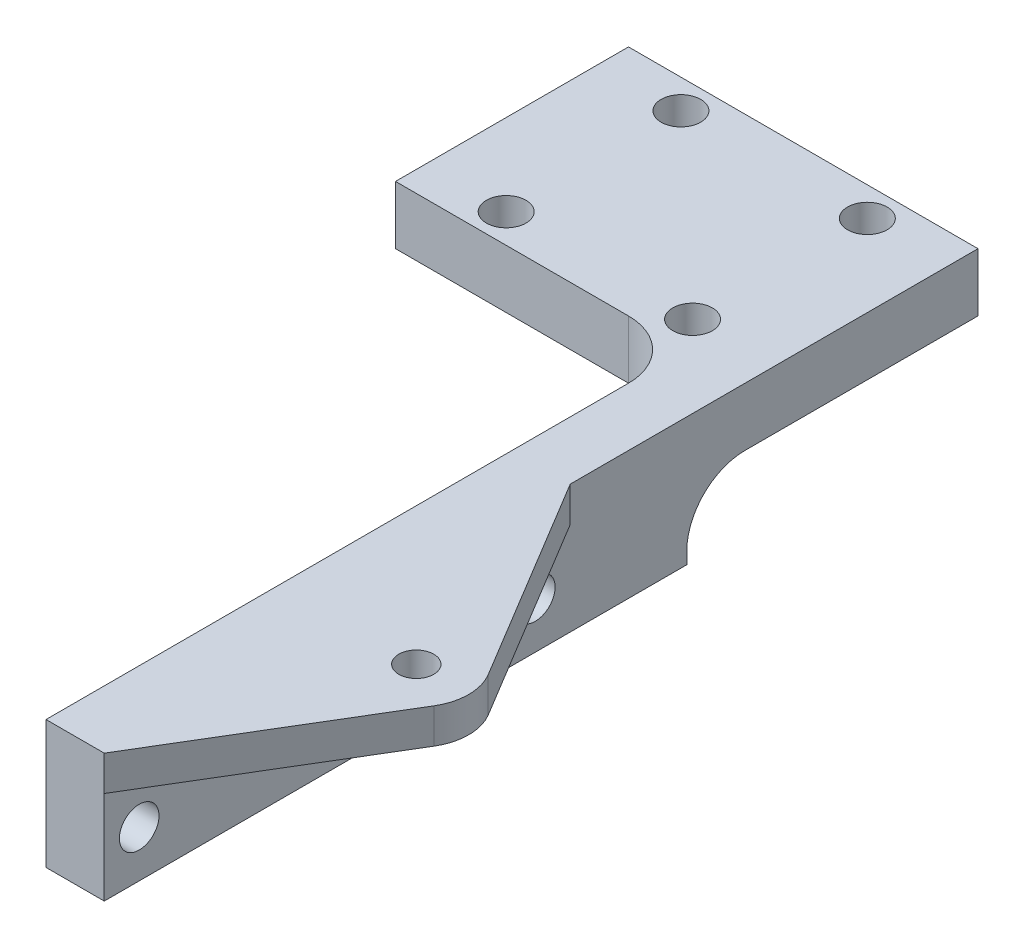
SolidWorks part; units mm, degrees
ref_plane "Front Plane" through (0, 0, 0) normal (0, 0, 1) x (1, 0, 0)
ref_plane "Top Plane" through (0, 0, 0) normal (0, 1, 0) x (1, 0, 0)
ref_plane "Right Plane" through (0, 0, 0) normal (1, 0, 0) x (0, 0, -1)
sketch "Sketch2" plane through (0, 0, 0) normal (1, 0, 0) x (0, 0, -1)
  line L0 (3.0688, 10.3579) -> (3.0688, 21.3579)
  line L1 (3.0688, 21.3579) -> (-36.9312, 21.3579)
  line L2 (-36.9312, 21.3579) -> (-36.9312, 10.3579)
  line L3 (-36.9312, 10.3579) -> (3.0688, 10.3579)
  line L5 (3.0688, 21.3579) -> (18.0688, 21.3579)
  line L6 (3.0688, 21.3579) -> (3.0688, 10.3579)
  line L7 (3.0688, 10.3579) -> (18.0688, 10.3579)
  line L8 (18.0688, 21.3579) -> (18.0688, 10.3579)
  circle A0 centre (0.0688, 14.3579) radius 1.7
  circle A1 centre (-33.9312, 14.3579) radius 1.7
extrude "Boss-Extrude1" add sketch "Sketch2" along normal blind 5 contours L8 L5 L0 L7 | L2 L3 L0 L1 A1 A0 region at (0, 15.9225, 16.9312) region at (0, 15.8579, -10.5688)
sketch "Sketch3" plane through (0, 21.3579, 0) normal (0, 1, 0) x (1, 0, 0)
  line L0 (-25, 38.0688) -> (-25, 18.0688)
  line L1 (-25, 18.0688) -> (5, 18.0688)
  line L2 (5, 18.0688) -> (5, 38.0688)
  line L3 (5, 38.0688) -> (-25, 38.0688)
  line L4 (0, -36.9312) -> (0, 18.0688) construction
  line L5 (0, -36.9312) -> (0, 18.0688)
  line L6 (5, -36.9312) -> (5, 18.0688) construction
  line L7 (5, -36.9312) -> (5, 18.0688)
  circle A0 centre (-2, 20.5688) radius 1.7
  circle A1 centre (-2, 35.5688) radius 1.7
  circle A2 centre (-18, 20.5688) radius 1.7
  circle A3 centre (-18, 35.5688) radius 1.7
  line M4 (5, 18.0688) -> (0, 18.0688)
extrude "Boss-Extrude2" add sketch "Sketch3" against normal blind 5 contours L2 L3 L0 L1 A3 A2 A1 A0 M4 region at (-10, 21.3579, -28.0688)
sketch "Sketch4" plane through (0, 0, -18.0688) normal (0, 0, -1) x (-1, 0, 0)
  line L4 (0, 10.3579) -> (0, 16.3579)
  line L5 (0, 16.3579) -> (-5, 16.3579)
  line L6 (-5, 16.3579) -> (-5, 10.3579)
  line L7 (-5, 10.3579) -> (0, 10.3579)
  line L8 (0, 10.3579) -> (0, 16.3579)
  line L9 (0, 16.3579) -> (-5, 16.3579)
  line L10 (-5, 16.3579) -> (-5, 10.3579)
  line L11 (-5, 10.3579) -> (0, 10.3579)
  dimension "D1" = 0
extrude "Cut-Extrude1" cut sketch "Sketch4" against normal blind 5
fillet "Fillet1" radius 5 1 edges at (2.5, 16.3579, -13.0688)
fillet "Fillet2" radius 5 1 edges at (0, 18.8579, -18.0688)
sketch "Sketch5" plane through (0, 21.3579, 0) normal (0, 1, 0) x (1, 0, 0)
  line L0 (5, -1.6312) -> (5, 1.7688) construction
  line L1 (5, -35.6312) -> (5, -32.2312) construction
  line L2 (5, -1.6312) -> (5, 1.7688)
  line L3 (5, -35.6312) -> (5, -32.2312)
  line L4 (5, -32.2312) -> (5, -1.6312)
  line L5 (5, -16.9312) -> (11.7846, -16.9312)
  line L6 (15.6402, -19.2516) -> (5, -36.9312)
  line L7 (15.6402, -14.6107) -> (5, 3.0688)
  line L14 (0, 13.0688) -> (0, -36.9312)
  line L15 (0, -36.9312) -> (5, -36.9312)
  line L16 (5, -36.9312) -> (5, 38.0688)
  line L17 (5, 38.0688) -> (-25, 38.0688)
  line L18 (-25, 38.0688) -> (-25, 18.0688)
  line L19 (-25, 18.0688) -> (-5, 18.0688)
  line L20 (0, 13.0688) -> (0, -36.9312)
  line L21 (0, -36.9312) -> (5, -36.9312)
  line L22 (5, -36.9312) -> (5, 38.0688)
  line L23 (5, 38.0688) -> (-25, 38.0688)
  line L24 (-25, 38.0688) -> (-25, 18.0688)
  line L25 (-25, 18.0688) -> (-5, 18.0688)
  circle A0 centre (11.7846, -16.9312) radius 1.5
  circle A1 centre (11.7846, -16.9312) radius 4.5
  arc A3 (0, 13.0688) -> (-5, 18.0688) centre (-5, 13.0688) ccw
  arc A4 (0, 13.0688) -> (-5, 18.0688) centre (-5, 13.0688) ccw
  line M12 (5, -36.9312) -> (5, 38.0688)
  dimension "D1" = 3
  dimension "D2" = 0
extrude "Boss-Extrude3" add sketch "Sketch5" against normal blind 3 contours A1 L5 L6 M12 | A1 L7 L4 L5 M12 | A1 A0 region at (7.9582, 21.3579, 8.5022) region at (7.9582, 21.3579, 25.3602) region at (10.6146, 21.3579, 12.7179)
sketch "Sketch6" plane through (0, 0, 36.9312) normal (0, 0, 1) x (1, 0, 0)
  line L5 (0, 21.3579) -> (0, 10.3579)
  line L6 (0, 10.3579) -> (5, 10.3579)
  line L7 (5, 10.3579) -> (5, 18.3579)
  line L8 (5, 18.3579) -> (5, 21.3579)
  line L9 (5, 21.3579) -> (0, 21.3579)
  line L10 (0, 21.3579) -> (0, 10.3579)
  line L11 (0, 10.3579) -> (5, 10.3579)
  line L12 (5, 10.3579) -> (5, 18.3579)
  line L13 (5, 18.3579) -> (5, 21.3579)
  line L14 (5, 21.3579) -> (0, 21.3579)
  dimension "D1" = 0
